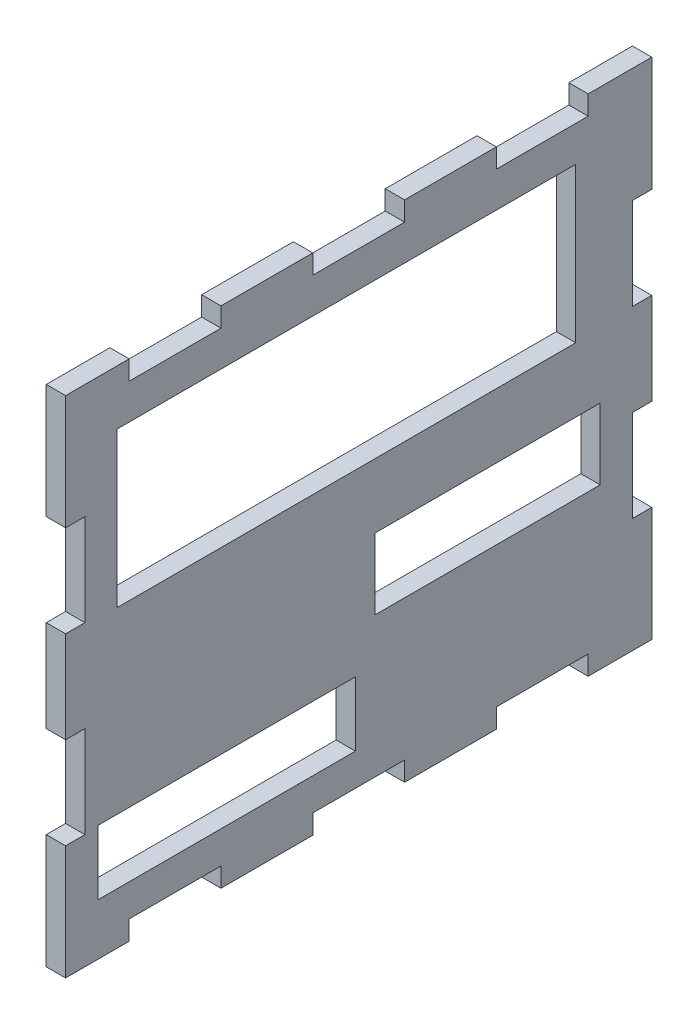
SolidWorks part; units mm, degrees
ref_plane "Front Plane" through (0, 0, 0) normal (0, 0, 1) x (1, 0, 0)
ref_plane "Top Plane" through (0, 0, 0) normal (0, 1, 0) x (1, 0, 0)
ref_plane "Right Plane" through (0, 0, 0) normal (1, 0, 0) x (0, 0, -1)
sketch "Sketch1" plane through (0, 0, 0) normal (1, 0, 0) x (0, 0, -1)
  line L148 (-46.8005, 37.0693) -> (-46.8005, 19.2943)
  line L149 (-46.8005, 19.2943) -> (-43.8005, 19.2943)
  line L150 (-43.8005, 19.2943) -> (-43.8005, 5.0443)
  line L151 (-43.8005, 5.0443) -> (-46.8005, 5.0443)
  line L152 (-46.8005, 5.0443) -> (-46.8005, -9.2057)
  line L153 (-46.8005, -9.2057) -> (-43.8005, -9.2057)
  line L154 (-43.8005, -9.2057) -> (-43.8005, -23.4557)
  line L155 (-43.8005, -23.4557) -> (-46.8005, -23.4557)
  line L156 (-46.8005, -23.4557) -> (-46.8005, -37.7057)
  line L157 (-46.8005, -37.7057) -> (-46.8005, -41.2307)
  line L158 (-46.8005, -41.2307) -> (-36.9255, -41.2307)
  line L159 (-36.9255, -41.2307) -> (-36.9255, -38.2307)
  line L160 (-36.9255, -38.2307) -> (-22.6755, -38.2307)
  line L161 (-22.6755, -38.2307) -> (-22.6755, -41.2307)
  line L162 (-22.6755, -41.2307) -> (-8.4255, -41.2307)
  line L163 (-8.4255, -41.2307) -> (-8.4255, -38.2307)
  line L164 (-8.4255, -38.2307) -> (5.8245, -38.2307)
  line L165 (5.8245, -38.2307) -> (5.8245, -41.2307)
  line L166 (5.8245, -41.2307) -> (20.0745, -41.2307)
  line L167 (20.0745, -41.2307) -> (20.0745, -38.2307)
  line L168 (20.0745, -38.2307) -> (34.3245, -38.2307)
  line L169 (34.3245, -38.2307) -> (34.3245, -41.2307)
  line L170 (34.3245, -41.2307) -> (44.1995, -41.2307)
  line L171 (44.1995, -41.2307) -> (44.1995, -23.4557)
  line L172 (44.1995, -23.4557) -> (41.1995, -23.4557)
  line L173 (41.1995, -23.4557) -> (41.1995, -9.2057)
  line L174 (41.1995, -9.2057) -> (44.1995, -9.2057)
  line L175 (44.1995, -9.2057) -> (44.1995, 5.0443)
  line L176 (44.1995, 5.0443) -> (41.1995, 5.0443)
  line L177 (41.1995, 5.0443) -> (41.1995, 19.2943)
  line L178 (41.1995, 19.2943) -> (44.1995, 19.2943)
  line L179 (44.1995, 19.2943) -> (44.1995, 33.5443)
  line L180 (44.1995, 33.5443) -> (44.1995, 37.0693)
  line L181 (44.1995, 37.0693) -> (34.3245, 37.0693)
  line L182 (34.3245, 37.0693) -> (34.3245, 34.0693)
  line L183 (34.3245, 34.0693) -> (20.0745, 34.0693)
  line L184 (20.0745, 34.0693) -> (20.0745, 37.0693)
  line L185 (20.0745, 37.0693) -> (5.8245, 37.0693)
  line L186 (5.8245, 37.0693) -> (5.8245, 34.0693)
  line L187 (5.8245, 34.0693) -> (-8.4255, 34.0693)
  line L188 (-8.4255, 34.0693) -> (-8.4255, 37.0693)
  line L189 (-8.4255, 37.0693) -> (-22.6755, 37.0693)
  line L190 (-22.6755, 37.0693) -> (-22.6755, 34.0693)
  line L191 (-22.6755, 34.0693) -> (-36.9255, 34.0693)
  line L192 (-36.9255, 34.0693) -> (-36.9255, 37.0693)
  line L193 (-36.9255, 37.0693) -> (-46.8005, 37.0693)
extrude "Boss-Extrude1" add sketch "Sketch1" along normal blind 3
sketch "Sketch2" plane through (3, 0, 0) normal (1, 0, 0) x (0, 0, -1)
  line L1 (-38.8005, 28.5693) -> (32.3995, 28.5693)
  line L2 (-38.8005, 28.5693) -> (-38.8005, 4.5693)
  line L3 (-38.8005, 4.5693) -> (32.3995, 4.5693)
  line L4 (32.3995, 28.5693) -> (32.3995, 4.5693)
  line L7 (1.1995, -5.4307) -> (36.1995, -5.4307)
  line L8 (1.1995, -5.4307) -> (1.1995, -16.4307)
  line L9 (1.1995, -16.4307) -> (36.1995, -16.4307)
  line L10 (36.1995, -5.4307) -> (36.1995, -16.4307)
  line L13 (-41.8005, -23.2307) -> (-1.8005, -23.2307)
  line L14 (-41.8005, -23.2307) -> (-41.8005, -33.2307)
  line L15 (-41.8005, -33.2307) -> (-1.8005, -33.2307)
  line L16 (-1.8005, -23.2307) -> (-1.8005, -33.2307)
  line L17 (-43.8005, -9.2057) -> (-43.8005, -23.4557) construction
  line L18 (-36.9255, -38.2307) -> (-22.6755, -38.2307) construction
  line L19 (41.1995, -23.4557) -> (41.1995, -9.2057) construction
  line L21 (-43.8005, 19.2943) -> (-43.8005, 5.0443) construction
  line L22 (34.3245, 34.0693) -> (20.0745, 34.0693) construction
  dimension "D2" = 42
  dimension "D3" = 15
  dimension "D4" = 35
  dimension "D5" = 5
  dimension "D6" = 11
  dimension "D7" = 40
  dimension "D8" = 5
  dimension "D9" = 10
  dimension "D10" = 24
  dimension "D11" = 71.2
  dimension "D12" = 5.5
  dimension "D13" = 10
extrude "Cut-Extrude1" cut sketch "Sketch2" against normal blind 3
